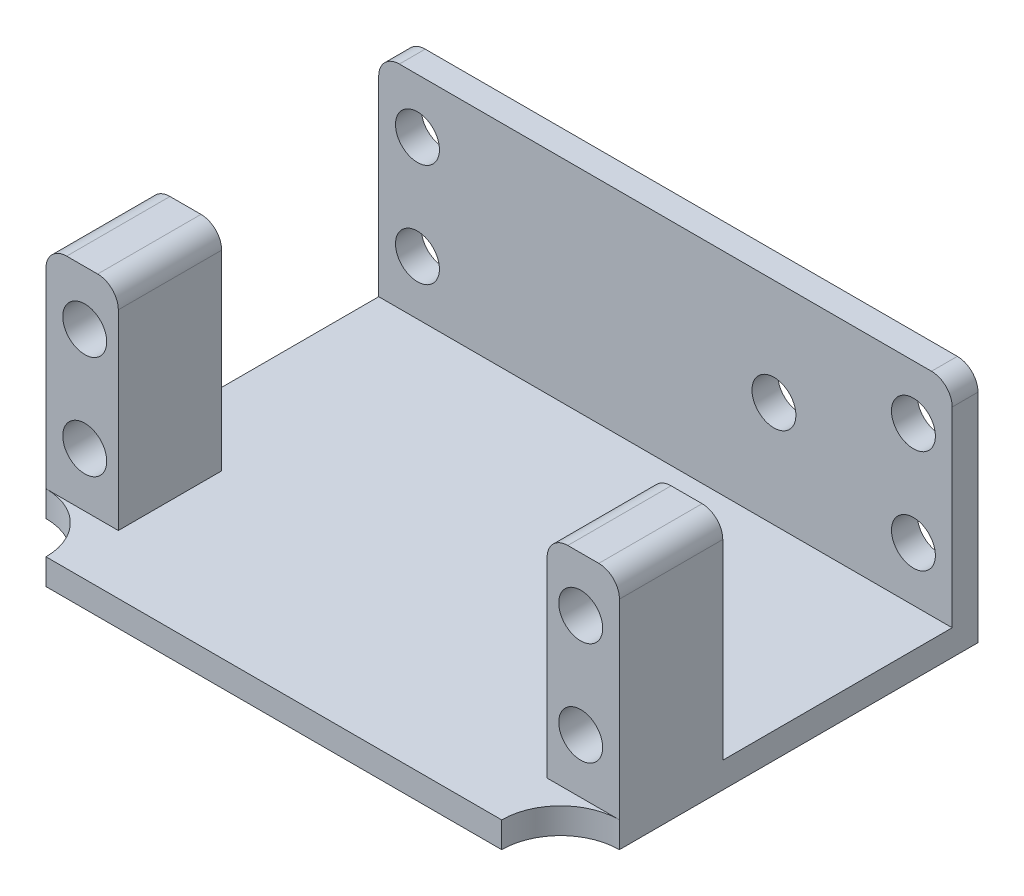
SolidWorks part; units mm, degrees
ref_plane "Front" through (0, 0, 0) normal (0, 0, 1) x (1, 0, 0)
ref_plane "Top" through (0, 0, 0) normal (0, 1, 0) x (1, 0, 0)
ref_plane "Right" through (0, 0, 0) normal (1, 0, 0) x (0, 0, -1)
sketch "Sketch1" plane through (0, 0, 0) normal (0, 1, 0) x (1, 0, 0)
  line L1 (0, 0) -> (55.5, 0)
  line L2 (0, 0) -> (0, 37.9)
  line L3 (0, 37.9) -> (55.5, 37.9)
  line L4 (55.5, 0) -> (55.5, 37.9)
  dimension "D1" = 37.9
  dimension "D2" = 55.5
extrude "bracketBase" add sketch "Sketch1" along normal blind 2.5
ref_plane "referencePlane1" through (0, 0, -8.2) normal (0, 0, 1) x (1, 0, 0)
sketch "Sketch2" plane through (0, 0, -8.2) normal (0, 0, 1) x (1, 0, 0)
  line L0 (27.75, 2.5) -> (27.75, 23) construction
  line L1 (0, 2.5) -> (7, 2.5)
  line L2 (0, 2.5) -> (0, 23)
  line L3 (0, 23) -> (7, 23)
  line L4 (7, 2.5) -> (7, 23)
  line L5 (0, 2.5) -> (55.5, 2.5) construction
  line L6 (55.5, 23) -> (48.5, 23)
  line L7 (48.5, 2.5) -> (48.5, 23)
  line L8 (55.5, 2.5) -> (48.5, 2.5)
  line L9 (55.5, 2.5) -> (55.5, 23)
  dimension "D1" = 20.5
  dimension "D2" = 7
extrude "servoMountingHoleTabs" add sketch "Sketch2" along normal blind 2.5
sketch "Sketch3" plane through (0, 0, -5.7) normal (0, 0, 1) x (1, 0, 0)
  line L0 (0, 12.75) -> (7, 12.75) construction
  line L3 (0, 23) -> (0, 2.5) construction
  line L4 (7, 2.5) -> (7, 23) construction
  line L5 (7, 23) -> (0, 23) construction
  line L6 (27.75, 2.5) -> (27.75, 23) construction
  line L7 (0, 2.5) -> (55.5, 2.5) construction
  circle A0 centre (3.75, 17.75) radius 2.125
  circle A1 centre (3.75, 7.75) radius 2.125
  circle A2 centre (51.75, 7.75) radius 2.125
  circle A3 centre (51.75, 17.75) radius 2.125
  dimension "D1" = 4.25
  dimension "D2" = 3.75
  dimension "D3" = 5.25
extrude "servoMountingHoles" cut sketch "Sketch3" against normal blind 2.5
sketch "Sketch4" plane through (0, 0, 0) normal (0, 1, 0) x (1, 0, 0)
  line L0 (55.5, 8.2) -> (55.5, 37.9) construction
  line L1 (0, 37.9) -> (55.5, 37.9)
  line L2 (0, 37.9) -> (0, 40.4)
  line L3 (0, 40.4) -> (55.5, 40.4)
  line L4 (55.5, 37.9) -> (55.5, 40.4)
  dimension "D1" = 2.5
extrude "baseWall" add sketch "Sketch4" along normal up to surface (23 mm away) up to face at (3.5, 23, -6.95)
sketch "Sketch6" plane through (0, 2.5, 0) normal (0, 1, 0) x (1, 0, 0)
  circle A0 centre (0, 0) radius 5.7
  circle A1 centre (55.5, 0) radius 5.7
extrude "baseTrim" cut sketch "Sketch6" against normal blind 2.5
fillet "Fillet1" radius 2 6 edges at (7, 23, -6.95) (48.5, 23, -6.95) (0, 23, -6.95) (55.5, 23, -6.95) (55.5, 23, -39.15) (0, 23, -39.15)
sketch "Sketch7" plane through (0, 0, -40.4) normal (0, 0, -1) x (-1, 0, 0)
  line L0 (0, 21) -> (0, 0) construction
  line L1 (-55.5, 0) -> (0, 0) construction
  circle A0 centre (-17.25, 12.75) radius 2.125
  dimension "D1" = 4.25
  dimension "D2" = 17.25
  dimension "D3" = 12.75
extrude "M4mountingHole" cut sketch "Sketch7" against normal blind 10
sketch "Sketch8" plane through (0, 0, -40.4) normal (0, 0, -1) x (-1, 0, 0)
  line L0 (-27.75, 23) -> (-27.75, 0) construction
  line L1 (-2, 23) -> (-53.5, 23) construction
  line L2 (-55.5, 0) -> (0, 0) construction
  circle A0 centre (-17.25, 12.75) radius 2.125 construction
  circle A1 centre (-17.25, 12.75) radius 2.125 construction
  circle A2 centre (-38.25, 12.75) radius 2.125
extrude "Cut-Extrude1" cut sketch "Sketch8" against normal blind 10
sketch "Sketch9" plane through (0, 0, -40.4) normal (0, 0, -1) x (-1, 0, 0)
  circle A0 centre (-17.25, 12.75) radius 2.125 construction
  circle A1 centre (-17.25, 12.75) radius 2.125
extrude "Boss-Extrude1" add sketch "Sketch9" against normal up to surface (2.5 mm away) up to face at (36.125, 12.75, -37.9)
sketch "Sketch10" plane through (0, 0, -8.2) normal (0, 0, -1) x (-1, 0, 0)
  line L4 (-48.5, 2.5) -> (-48.5, 21)
  line L5 (-50.5, 23) -> (-53.5, 23)
  line L6 (-55.5, 21) -> (-55.5, 2.5)
  line L7 (-55.5, 2.5) -> (-48.5, 2.5)
  line L8 (-48.5, 2.5) -> (-48.5, 21)
  line L9 (-50.5, 23) -> (-53.5, 23)
  line L10 (-55.5, 21) -> (-55.5, 2.5)
  line L11 (-55.5, 2.5) -> (-48.5, 2.5)
  line L12 (-2, 23) -> (-5, 23)
  line L13 (-7, 21) -> (-7, 2.5)
  line L14 (-7, 2.5) -> (0, 2.5)
  line L15 (0, 2.5) -> (0, 21)
  line L16 (-2, 23) -> (-5, 23)
  line L17 (-7, 21) -> (-7, 2.5)
  line L18 (-7, 2.5) -> (0, 2.5)
  line L19 (0, 2.5) -> (0, 21)
  circle A0 centre (-51.75, 17.75) radius 2.125 construction
  circle A1 centre (-51.75, 17.75) radius 2.125
  arc A2 (-48.5, 21) -> (-50.5, 23) centre (-50.5, 21) ccw
  arc A3 (-53.5, 23) -> (-55.5, 21) centre (-53.5, 21) ccw
  arc A4 (-48.5, 21) -> (-50.5, 23) centre (-50.5, 21) ccw
  arc A5 (-53.5, 23) -> (-55.5, 21) centre (-53.5, 21) ccw
  arc A6 (-5, 23) -> (-7, 21) centre (-5, 21) ccw
  arc A7 (0, 21) -> (-2, 23) centre (-2, 21) ccw
  arc A8 (-5, 23) -> (-7, 21) centre (-5, 21) ccw
  arc A9 (0, 21) -> (-2, 23) centre (-2, 21) ccw
  circle A10 centre (-51.75, 7.75) radius 2.125 construction
  circle A11 centre (-51.75, 7.75) radius 2.125
  circle A12 centre (-3.75, 17.75) radius 2.125 construction
  circle A13 centre (-3.75, 17.75) radius 2.125
  circle A14 centre (-3.75, 7.75) radius 2.125 construction
  circle A15 centre (-3.75, 7.75) radius 2.125
  dimension "D1" = 0
  dimension "D2" = 0
extrude "Boss-Extrude2" add sketch "Sketch10" along normal blind 7.5
sketch "Sketch11" plane through (0, 0, -5.7) normal (0, 0, 1) x (1, 0, 0)
  circle A0 centre (3.75, 17.75) radius 2.125 construction
  circle A1 centre (3.75, 17.75) radius 2.125
  circle A2 centre (3.75, 7.75) radius 2.125 construction
  circle A3 centre (3.75, 7.75) radius 2.125
  circle A4 centre (51.75, 17.75) radius 2.125 construction
  circle A5 centre (51.75, 17.75) radius 2.125
  circle A6 centre (51.75, 7.75) radius 2.125 construction
  circle A7 centre (51.75, 7.75) radius 2.125
extrude "Cut-Extrude2" cut sketch "Sketch11" against normal through all
